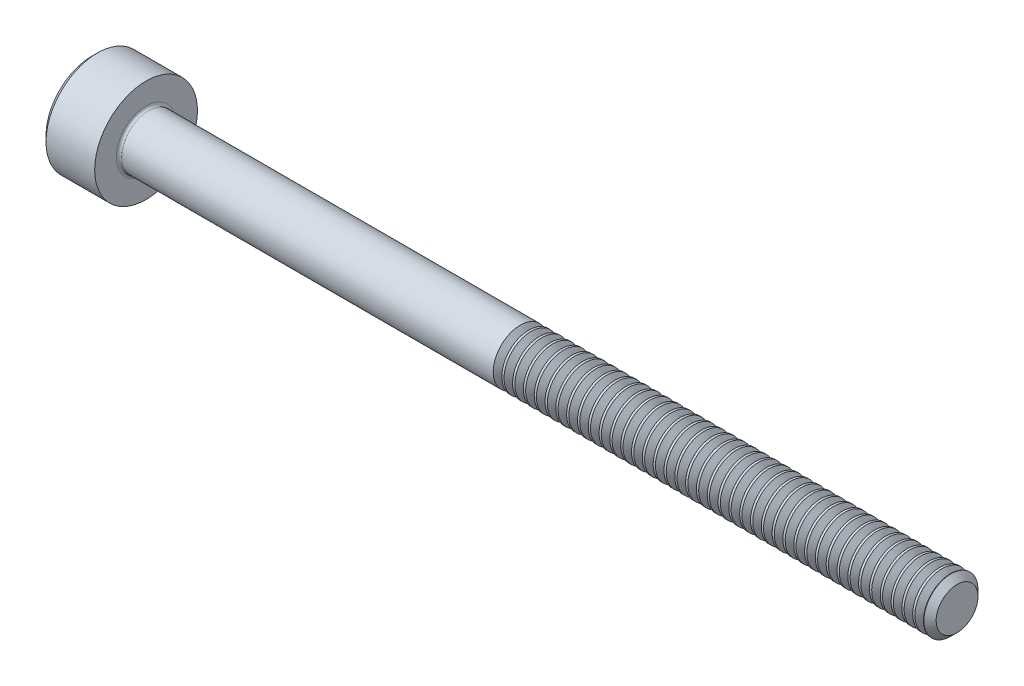
SolidWorks part; units mm, degrees
revolve "Base-Revolve" add sketch "BodySke"
sketch "BodySke" plane through (0, 0, 0) normal (0, 0, 1) x (1, 0, 0)
  line L0 (0, 0) -> (0, 1.7)
  line L1 (0.2, 1.9) -> (2, 1.9)
  line L2 (2, 1.9) -> (2, 1)
  line L3 (2, 1) -> (31.774, 1)
  line L4 (32, 0.774) -> (32, 0)
  line L5 (32, 0) -> (0, 0)
  line L6 (-31.75, 0) -> (127, 0) construction
  line L7 (0, 1.7) -> (0.2, 1.9)
  line L8 (32, 0.774) -> (31.774, 1)
  line L9 (0, -1.7) -> (0.2, -1.9) construction
  line L10 (32, -0.774) -> (31.774, -1) construction
  line L11 (2.4, 9.525) -> (2.4, 3.175) construction
  line L12 (16, 9.525) -> (16, 3.175) construction
  line L13 (-18, 9.525) -> (-18, 3.175) construction
  dimension "Diameter" = 2
  dimension "Head_ht" = 2
  dimension "Length" = 30
  dimension "Body_ch_ang" = 45
  dimension "Head_dia" = 3.8
  dimension "Head_ch_ang" = 45
  dimension "Minor_dia" = 1.548
  dimension "Advance" = 0.4
  dimension "Thread_nom" = 16
  dimension "Thread_length" = 50
  dimension "Head_ch_ht" = 0.2
cosmetic thread "ThreadCosmetic" [suppressed]
fillet "Fillet1" radius 0.1 1 edges at (2, 0, 1)
ref_plane "Plane1" through (0, 0, 0) normal (0, 0, 1) x (1, 0, 0)
ref_plane "Plane2" through (0, 0, 0) normal (0, 1, 0) x (1, 0, 0)
ref_plane "Plane3" through (0, 0, 0) normal (1, 0, 0) x (0, 0, -1)
other "Configuration Table"
sketch "Sketch2" plane through (0, 0, 0) normal (0, 0, 1) x (1, 0, 0)
  line L0 (0, 0.7725) -> (1, 0.7725)
  line L1 (1, 0.7725) -> (1.446, 0)
  line L2 (-31.75, 0) -> (127, 0) construction
  line L3 (1.446, 0) -> (0, 0)
  line L4 (0, 0) -> (0, 0.7725)
  line L5 (0, 1.7) -> (0, -1.7) construction
  line L6 (0, 0) -> (47.625, 0) construction
  line L7 (2, -1.9) -> (2, 1.9) construction
  dimension "D1" = 0.7725
  dimension "D2" = 60
revolve "Hex-PreBroach" cut sketch "Sketch2" angle 360 about L6
sketch "Sketch3" plane through (0, 0, 0) normal (-1, 0, 0) x (0, 0.5, 0.866)
  line L0 (0.446, 0.7725) -> (-0.446, 0.7725)
  line L1 (-0.446, 0.7725) -> (-0.892, 0)
  line L2 (0.446, 0.7725) -> (0.892, 0)
  line L3 (0.446, -0.7725) -> (0.892, 0)
  line L4 (0.446, -0.7725) -> (-0.446, -0.7725)
  line L5 (-0.446, -0.7725) -> (-0.892, 0)
  dimension "D1" = 0.7725
  dimension "D2" = 0.7725
extrude "Hex" cut sketch "Sketch3" against normal blind 1
sketch "Sketch4" plane through (0, 0, 0) normal (-1, 0, 0) x (0, 0, 1)
  line L0 (0, 0) -> (0.9398, 0)
  line L1 (0, 0) -> (6.1484, 3.5498) construction
  line L2 (0, 0) -> (0.4699, 0.8139)
  line L3 (0.7832, 0.2175) -> (0.8962, 0.2828)
  line L4 (0.58, 0.5695) -> (0.693, 0.6348)
  arc A0 (0.7832, 0.2175) -> (0.58, 0.5695) centre (0, 0) ccw
  arc A1 (0.9398, 0) -> (0.8962, 0.2828) centre (0, 0) ccw
  arc A2 (0.4699, 0.8139) -> (0.693, 0.6348) centre (0, 0) cw
  dimension "D1" = 30
  dimension "D2" = 60
  dimension "Spline_p_dim" = 0.4064
  dimension "D3" = 0.2032
extrude "Spline" [suppressed] cut sketch "Sketch4"
pattern_circular "CirPattern1" [suppressed] count 6 every 60
sketch "Sketch5" plane through (0, 0, 0) normal (0, 0, 1) x (1, 0, 0)
  line L0 (-31.75, 0) -> (127, 0) construction
  line L2 (0, 1.7) -> (0, -1.7) construction
  circle A0 centre (0.1, 0) radius 0.005
  dimension "Drilled_hole_dia" = 0.01
  dimension "Drilled_hole_loc" = 0.1
extrude "Hole" [suppressed] cut sketch "Sketch5"
pattern_circular "Drilled-4" [suppressed] count 2 every 60
pattern_circular "Drilled-6" [suppressed] count 3 every 60
sketch "ThdSchSke" plane through (0, 0, 0) normal (0, 0, 1) x (1, 0, 0)
  line L0 (16, -0.774) -> (15.8418, -1)
  line L1 (16, -0.774) -> (16.1582, -1)
  line L2 (16.1582, -1) -> (16.1582, -1.25)
  line L3 (-3.175, 0) -> (5.1513, 0) construction
  line L5 (16.1582, -1.25) -> (15.8418, -1.25)
  line L6 (15.8418, -1.25) -> (15.8418, -1)
  line L7 (0, 1.7) -> (0, -1.7) construction
  dimension "Thread_minor" = 1.548
  dimension "Diameter" = 2
  dimension "Start" = 16
revolve "ThreadSchematic" cut sketch "ThdSchSke" angle 360 about L3
pattern_linear "ThdSchPat" count 40 spacing 0.4 along (1, 0, 0) of "ThreadSchematic"
equation "\"D2@Sketch3\" = \"Hex_size@Sketch3\" / 2"
equation "\"D1@Sketch3\" = \"Hex_size@Sketch3\" / 2"
equation "\"D1@Sketch2\" = \"Hex_size@Sketch3\" / 2"
equation "\"D3@Sketch4\" = \"Spline_p_dim@Sketch4\" / 2"
equation "\"Thread_minor@ThreadCosmetic\"  =  \"Minor_dia@BodySke\""
equation "\"D2@CirPattern1\" = 360 / \"Num_teeth@CirPattern1\""
equation "\"Wall_thickness@Sketch2\" = \"Head_ht@BodySke\" - \"Key_eng@Hex\""
equation "\"Thread_length@ThreadCosmetic\" = ((sgn( (\"Length@BodySke\" - \"Advance@BodySke\" ) - \"Thread_nom@BodySke\" )-1)*( (\"Length@BodySke\" - \"Advance@BodySke\" ) - \"Thread_nom@BodySke\" ))/-2+ \"Thread_nom@BodySke\""
equation "\"Thread_minor@ThdSchSke\" = \"Minor_dia@BodySke\""
equation "\"Diameter@ThdSchSke\" = \"Diameter@BodySke\""
equation "\"Overcut@ThdSchSke\" = \"Diameter@BodySke\" * 1.25"
equation "\"Start@ThdSchSke\" = \"Head_ht@BodySke\" + \"Length@BodySke\" - \"Thread_length@ThreadCosmetic\"  '---Non-countersunk---"
equation "\"Num_threads@ThdSchPat\" = int( \"Thread_length@ThreadCosmetic\" / \"Advance@BodySke\" + 0.999 )  + 1"
equation "\"Advance@ThdSchPat\" = \"Thread_length@ThreadCosmetic\" /  (\"Num_threads@ThdSchPat\" - 1) 'relax it"
equation "\"Num_threads@ThdSchPat\" = \"Num_threads@ThdSchPat\" - sgn( \"Num_threads@ThdSchPat\" - 1) '---chamfered tips only---"
